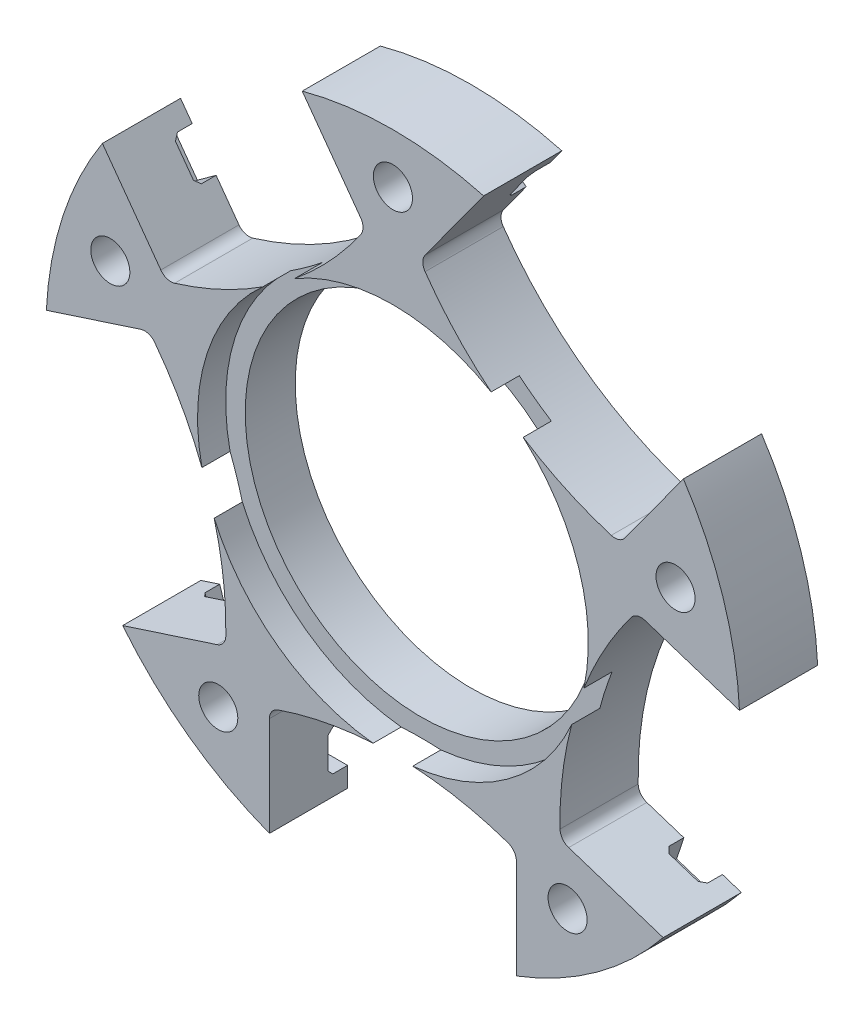
SolidWorks part; units mm, degrees
ref_plane "Front Plane" through (0, 0, 0) normal (0, 0, 1) x (1, 0, 0)
ref_plane "Top Plane" through (0, 0, 0) normal (0, 1, 0) x (1, 0, 0)
ref_plane "Right Plane" through (0, 0, 0) normal (1, 0, 0) x (0, 0, -1)
sketch "Sketch1" plane through (0, 0, 0) normal (0, 0, 1) x (1, 0, 0)
  circle A0 centre (0, 0) radius 15.875
  circle A1 centre (0, 0) radius 14.2875
  circle A2 centre (0, 0) radius 28.194
  dimension "D1" = 31.75
  dimension "D2" = 28.575
  dimension "D3" = 56.388
extrude "Boss-Extrude1" add sketch "Sketch1" against normal blind 6.35 contours A2 A0 | A0 A1 region at (-15.426, 0, 0) region at (-27.3966, 0, 0)
extrude "Cut-Extrude1" cut sketch "Sketch1<3>" against normal blind 2.286 contours A0 A1 region at (-15.426, 0, 0)
sketch "Sketch1<3>" plane through (0, 0, 0) normal (0, 0, 1) x (1, 0, 0) same geometry as "Sketch1"
sketch "Sketch2" plane through (0, 0, 0) normal (0, 0, 1) x (1, 0, 0)
  line L1 (-10.033, -28.194) -> (10.033, -28.194)
  line L2 (-10.033, -28.194) -> (-10.033, -18.2735)
  line L4 (10.033, -28.194) -> (10.033, -18.2735)
  arc A0 (-9.3479, -17.3129) -> (9.3479, -17.3129) centre (0, -44.45) cw
  circle A2 centre (0, 0) radius 28.194 construction
  arc A3 (10.033, -18.2735) -> (9.3479, -17.3129) centre (9.017, -18.2735) ccw
  arc A4 (-10.033, -18.2735) -> (-9.3479, -17.3129) centre (-9.017, -18.2735) cw
  point P1 (0, -28.194)
  point P15 (10.033, -17.5587)
  point P18 (-10.033, -17.5587)
  dimension "D2" = 28.702
  dimension "D3" = 12.446
  dimension "D4" = 1.016
  dimension "D1" = 20.066
extrude "Cut-Extrude5" cut sketch "Sketch2" against normal through all
pattern_circular "CirPattern1" count 5 over 360 about axis through (0, 0, 0) along (0, 0, 1) of "Cut-Extrude5"
sketch "Sketch3" plane through (-10.033, 0, 0) normal (1, 0, 0) x (0, 0, -1)
  line L0 (6.35, -21.4335) -> (5.1511, -21.4335)
  line L1 (6.35, -26.3484) -> (6.35, -17.6841) construction
  line L2 (5.1511, -21.4335) -> (4.7498, -21.8349)
  line L3 (4.7498, -21.8349) -> (4.7498, -24.3342)
  line L4 (4.7498, -24.3342) -> (5.1511, -24.7355)
  line L5 (5.1511, -24.7355) -> (6.35, -24.7355)
  line L6 (6.35, -24.7355) -> (6.35, -21.4335)
  line L7 (6.35, -26.3484) -> (0, -26.3484) construction
  point P4 (3.8675, -22.8105)
  point P9 (0, 0)
  point P12 (4.7498, -23.0845)
  point P13 (6.35, -23.0845)
  point P14 (4.7498, -21.8867)
  dimension "D1" = 3.302
  dimension "D2" = 1.6002
  dimension "D3" = 1.1989
  dimension "D4" = 1.6129
  dimension "D5" = 45
extrude "Cut-Extrude6" cut sketch "Sketch3" against normal blind 1.8796
mirror "Mirror1" about plane through (0, 0, 0) normal (1, 0, 0) of "Cut-Extrude6"
pattern_circular "CirPattern2" count 5 over 360 about axis through (0, 0, -6.35) along (0, 0, 1) of "Cut-Extrude6", "Mirror1"
sketch "Sketch4" plane through (0, 0, -6.35) normal (0, 0, -1) x (-1, 0, 0)
  line L0 (-13.7761, -14.8269) -> (-9.8442, -17.6836) construction
  line L1 (-11.8101, -16.2552) -> (-16.572, -22.8094) construction
  arc A1 (-14.2788, -15.1888) -> (-13.5769, -14.2404) centre (-14.5927, -14.2225) ccw construction
  arc A2 (-9.3479, -17.3129) -> (-10.033, -18.2735) centre (-9.017, -18.2735) ccw construction
  arc A3 (-21.9585, -17.6841) -> (-10.033, -26.3484) centre (0, 0) ccw construction
  circle A4 centre (-14.1911, -19.5323) radius 1.5875
  dimension "D1" = 3.175
extrude "Cut-Extrude7" cut sketch "Sketch4" against normal through all
pattern_circular "CirPattern3" count 5 over 360 about axis through (0, 0, -6.35) along (0, 0, 1) of "Cut-Extrude7"
